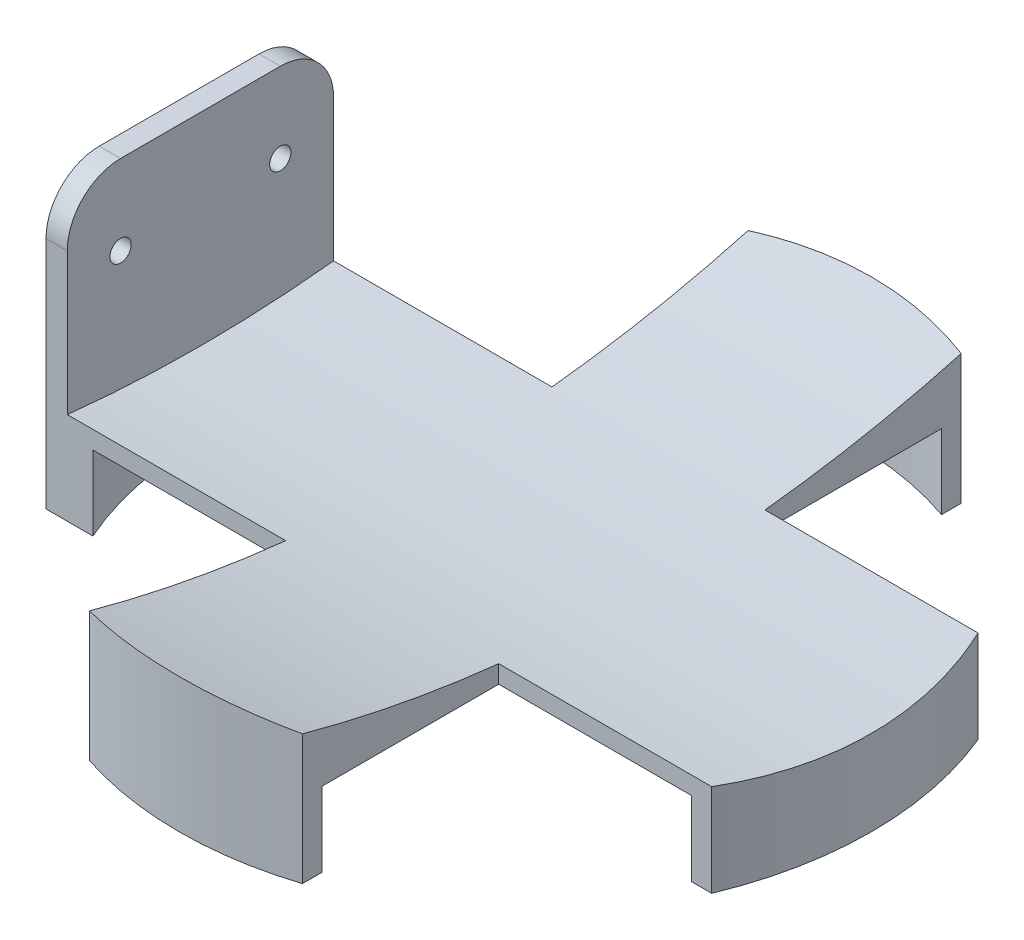
SolidWorks part; units mm, degrees
ref_plane "前视基准面" through (0, 0, 0) normal (0, 0, 1) x (1, 0, 0)
ref_plane "上视基准面" through (0, 0, 0) normal (0, 1, 0) x (1, 0, 0)
ref_plane "右视基准面" through (0, 0, 0) normal (1, 0, 0) x (0, 0, -1)
sketch "草图1" plane through (0, 0, 0) normal (1, 0, 0) x (0, 0, -1)
  line L1 (-25, 0) -> (25, 0)
  line L2 (-25, 0) -> (-25, -40)
  line L3 (-25, -40) -> (25, -40)
  line L4 (25, 0) -> (25, -40)
  dimension "D1" = 50
  dimension "D2" = 25
  dimension "D3" = 40
extrude "凸台-拉伸1" add sketch "草图1" along normal blind 4
sketch "草图2" plane through (4, 0, 0) normal (1, 0, 0) x (0, 0, -1)
  line L1 (-15, -15) -> (15, -15) construction
  line L2 (25, 0) -> (-25, 0) construction
  circle A0 centre (-15, -15) radius 2
  circle A1 centre (15, -15) radius 2
  dimension "D4" = 4
  dimension "D5" = 4
  dimension "D1" = 30
  dimension "D2" = 15
  dimension "D3" = 15
extrude "切除-拉伸1" cut sketch "草图2" against normal blind 4
sketch "草图3" plane through (4, 0, 0) normal (1, 0, 0) x (0, 0, -1)
  line L0 (-25, -40) -> (25, -40) construction
  line L1 (-25, -36.6549) -> (-25, -38.6664)
  line L2 (-25, 0) -> (-25, -40) construction
  line L6 (25, -40) -> (25, 0) construction
  line L7 (25, -38.6664) -> (25, -36.6549)
  arc A0 (-25, -36.6549) -> (25, -36.6549) centre (0, 195) ccw
  arc A1 (-25, -38.6664) -> (25, -38.6664) centre (0, 195) ccw
  dimension "D1" = 466
  dimension "D2" = 470
extrude "凸台-拉伸2" add sketch "草图3" along normal blind 180
sketch "草图4" plane through (4, 0, 0) normal (1, 0, 0) x (0, 0, -1)
  line L2 (0, -40) -> (25, -40)
  line L3 (25, -40) -> (25, -38.6664)
  line L4 (0, -40) -> (25, -40)
  line L5 (25, -40) -> (25, -38.6664)
  line L6 (-25, -38.6664) -> (-25, -40)
  line L7 (-25, -40) -> (0, -40)
  line L8 (-25, -38.6664) -> (-25, -40)
  line L9 (-25, -40) -> (0, -40)
  arc A1 (0, -40) -> (25, -38.6664) centre (0, 195) ccw
  arc A2 (0, -40) -> (25, -38.6664) centre (0, 195) ccw
  arc A3 (-25, -38.6664) -> (0, -40) centre (0, 195) ccw
  arc A4 (-25, -38.6664) -> (0, -40) centre (0, 195) ccw
  arc M7 (25, -38.6664) -> (0, -40) centre (0, 195) cw
  line M8 (0, -40) -> (25, -40)
  line M9 (25, -40) -> (25, -38.6664)
  dimension "D1" = 0
  dimension "D2" = 0
extrude "切除-拉伸2" cut sketch "草图4" against normal blind 60 contours M9 M7 M8 region at (4, -39.6001, -18.7536)
sketch "草图5" plane through (4, 0, 0) normal (1, 0, 0) x (0, 0, -1)
  line L2 (-25, -38.6664) -> (-25, -40)
  line L3 (-25, -40) -> (0, -40)
  line L4 (-25, -38.6664) -> (-25, -40)
  line L5 (-25, -40) -> (0, -40)
  arc A1 (-25, -38.6664) -> (0, -40) centre (0, 195) ccw
  arc A2 (-25, -38.6664) -> (0, -40) centre (0, 195) ccw
  dimension "D1" = 0
extrude "切除-拉伸3" cut sketch "草图5" against normal blind 60
ref_plane "基准面1" through (0, -40, 0) normal (0, -1, 0) x (-1, 0, 0)
sketch "草图6" plane through (0, -40, 0) normal (0, -1, 0) x (-1, 0, 0)
  line L2 (-85.0023, 61.8458) -> (-85.0023, 25)
  line L4 (-45.0023, 61.8473) -> (-45.0023, 25)
  line L5 (-125, 25) -> (-85.0023, 25)
  line L7 (-125, -25) -> (-85.0023, -25)
  line L9 (-85.0023, -25) -> (-85.0023, -61.8458)
  line L10 (-45.0023, -25) -> (-45.0023, -61.8473)
  line L11 (-45.0023, 25) -> (-5, 25)
  line L12 (-45.0023, -25) -> (-5, -25)
  arc A0 (-5, -25) -> (-5, 25) centre (-65, 0) ccw
  arc A1 (-85.0023, -61.8458) -> (-45.0023, -61.8473) centre (-65, 0) ccw
  arc A2 (-125, 25) -> (-125, -25) centre (-65, 0) ccw
  arc A3 (-45.0023, 61.8473) -> (-85.0023, 61.8458) centre (-65, 0) ccw
  dimension "D1" = 130
  dimension "D2" = 50
  dimension "D3" = 40
  dimension "D4" = 25
  dimension "D5" = 65
  dimension "D7" = 45.0023
extrude "凸台-拉伸3" add sketch "草图6" against normal up to surface (3.3451 mm away) up to face at (94, -37.3275, 0)
mirror "镜向1" about plane through (0, 0, 0) normal (0, 0, 1) of "凸台-拉伸3"
sketch "草图7" plane through (0, -40, 0) normal (0, -1, 0) x (1, 0, 0)
  line L8 (5, -25) -> (45.0023, -25)
  line L9 (45.0023, -25) -> (45.0023, -61.8473)
  line L10 (85.0023, -61.8458) -> (85.0023, -25)
  line L11 (85.0023, -25) -> (125, -25)
  line L12 (125, 25) -> (85.0023, 25)
  line L13 (85.0023, 25) -> (85.0023, 61.8458)
  line L14 (45.0023, 61.8473) -> (45.0023, 25)
  line L15 (45.0023, 25) -> (5, 25)
  line L16 (5, -25) -> (8.8106, -25)
  line L17 (45.0023, -58.1579) -> (45.0023, -61.8473)
  line L18 (85.0023, -61.8458) -> (85.0023, -58.1563)
  line L19 (121.1894, -25) -> (125, -25)
  line L20 (125, 25) -> (121.1894, 25)
  line L21 (85.0023, 58.1563) -> (85.0023, 61.8458)
  line L22 (45.0023, 61.8473) -> (45.0023, 58.1579)
  line L23 (8.8106, 25) -> (5, 25)
  arc A0 (8.8106, 25) -> (8.8106, -25) centre (65, 0) ccw
  arc A1 (85.0023, 58.1563) -> (45.0023, 58.1579) centre (65, 0) ccw
  arc A2 (121.1894, -25) -> (121.1894, 25) centre (65, 0) ccw
  arc A3 (45.0023, -58.1579) -> (85.0023, -58.1563) centre (65, 0) ccw
  arc A7 (5, 25) -> (0, 0) centre (65, 0) ccw
  arc A8 (0, 0) -> (5, -25) centre (65, 0) ccw
  arc A9 (45.0023, -61.8473) -> (85.0023, -61.8458) centre (65, 0) ccw
  arc A10 (125, -25) -> (130, 0) centre (65, 0) ccw
  arc A11 (130, 0) -> (125, 25) centre (65, 0) ccw
  arc A12 (85.0023, 61.8458) -> (45.0023, 61.8473) centre (65, 0) ccw
  arc A13 (5, 25) -> (0, 0) centre (65, 0) ccw
  arc A14 (0, 0) -> (5, -25) centre (65, 0) ccw
  arc A15 (45.0023, -61.8473) -> (85.0023, -61.8458) centre (65, 0) ccw
  arc A16 (125, -25) -> (130, 0) centre (65, 0) ccw
  arc A17 (130, 0) -> (125, 25) centre (65, 0) ccw
  arc A18 (85.0023, 61.8458) -> (45.0023, 61.8473) centre (65, 0) ccw
  dimension "D1" = 123
  dimension "D2" = 65
  dimension "D3" = 0
extrude "凸台-拉伸4" add sketch "草图7" along normal blind 14
sketch "草图8" plane through (0, -54, 0) normal (0, -1, 0) x (1, 0, 0)
  line L3 (184, 25) -> (125, 25)
  line L4 (125, -25) -> (184, -25)
  line L5 (184, -25) -> (184, 25)
  line L6 (184, 25) -> (125, 25)
  line L7 (125, -25) -> (184, -25)
  line L8 (184, -25) -> (184, 25)
  arc A1 (125, -25) -> (125, 25) centre (65, 0) ccw
  arc A2 (125, -25) -> (125, 25) centre (65, 0) ccw
  dimension "D1" = 0
extrude "切除-拉伸4" cut sketch "草图8" against normal through all
sketch "草图11" plane through (0, -54, 0) normal (0, -1, 0) x (1, 0, 0)
  line L2 (0, 25) -> (0, 0)
  line L3 (5, 25) -> (0, 25)
  line L4 (0, 25) -> (0, 0)
  line L5 (5, 25) -> (0, 25)
  arc A1 (5, 25) -> (0, 0) centre (65, 0) ccw
  arc A2 (5, 25) -> (0, 0) centre (65, 0) ccw
  dimension "D1" = 0
extrude "凸台-拉伸6" add sketch "草图11" against normal up to next
sketch "草图12" plane through (0, -54, 0) normal (0, -1, 0) x (1, 0, 0)
  line L2 (0, -25) -> (5, -25)
  line L3 (0, 0) -> (0, -25)
  line L4 (0, -25) -> (5, -25)
  line L5 (0, 0) -> (0, -25)
  arc A1 (0, 0) -> (5, -25) centre (65, 0) ccw
  arc A2 (0, 0) -> (5, -25) centre (65, 0) ccw
  dimension "D1" = 0
extrude "凸台-拉伸7" add sketch "草图12" against normal up to next
fillet "圆角1" radius 10 2 edges at (2, 0, 25) (2, 0, -25)
